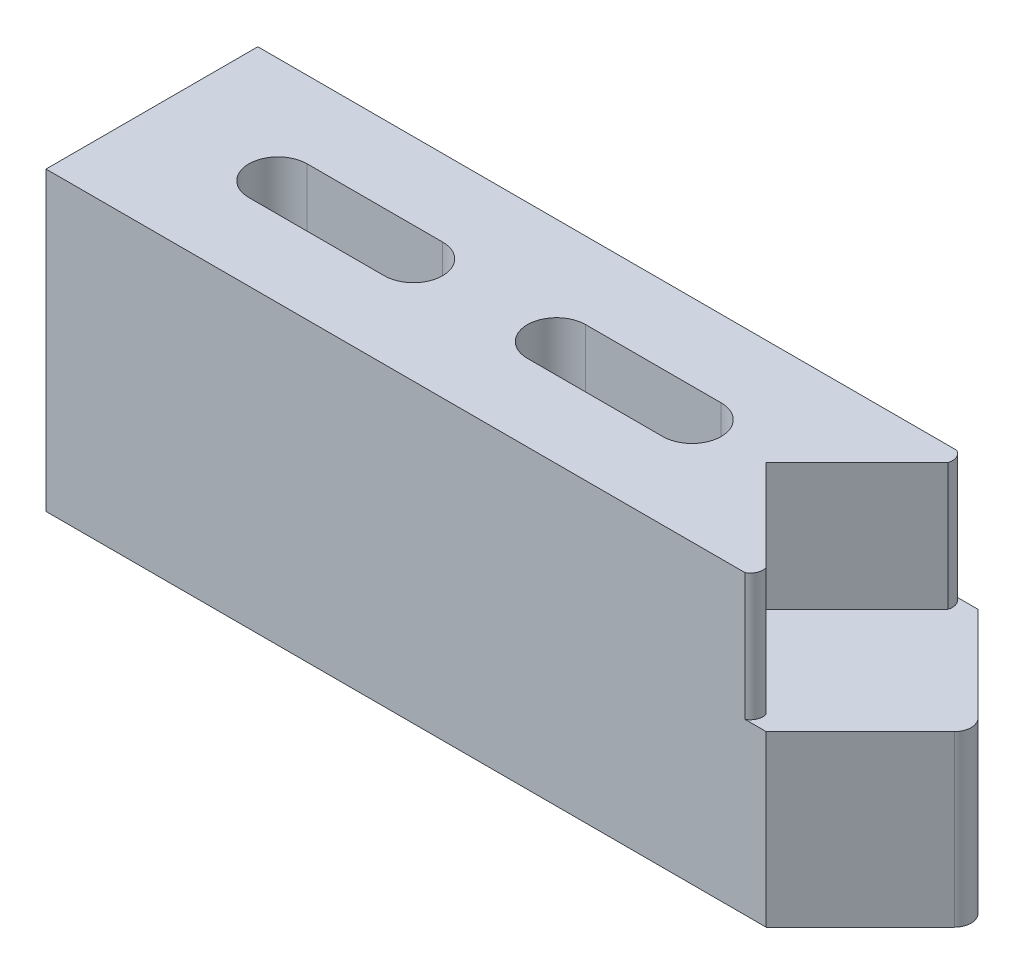
SolidWorks part; units mm, degrees
ref_plane "Front Plane" through (0, 0, 0) normal (0, 0, 1) x (1, 0, 0)
ref_plane "Top Plane" through (0, 0, 0) normal (0, 1, 0) x (1, 0, 0)
ref_plane "Right Plane" through (0, 0, 0) normal (1, 0, 0) x (0, 0, -1)
sketch "Sketch1" plane through (0, 0, 0) normal (0, 0, 1) x (1, 0, 0)
  line L0 (0, 0) -> (43.18, 0)
  line L6 (0, 0) -> (0, 17.78)
  line L10 (0, 17.78) -> (43.18, 17.78)
  line L11 (43.18, 0) -> (43.18, 17.78)
  dimension "D1" = 43.18
  dimension "D2" = 17.78
extrude "Boss-Extrude1" add sketch "Sketch1" against normal blind 12.7
sketch "Sketch3" plane through (0, 17.78, 0) normal (0, 1, 0) x (1, 0, 0)
  line L0 (43.18, 12.7) -> (36.83, 6.35)
  line L1 (36.83, 6.35) -> (43.18, 0)
  line L4 (43.18, 12.7) -> (43.18, 0)
  dimension "D2" = 90
extrude "Cut-Extrude1" cut sketch "Sketch3" against normal blind 7.62
sketch "Sketch4" plane through (0, 17.78, 0) normal (0, 1, 0) x (1, 0, 0)
  line L0 (32.381, 6.35) -> (24.261, 6.35) construction
  line L1 (32.381, 4.6) -> (24.261, 4.6)
  line L2 (32.381, 8.1) -> (24.261, 8.1)
  line L3 (15.681, 6.35) -> (7.561, 6.35) construction
  line L4 (15.681, 4.6) -> (7.561, 4.6)
  line L5 (15.681, 8.1) -> (7.561, 8.1)
  line L6 (43.18, 0) -> (0, 0) construction
  line L7 (0, 12.7) -> (0, 0) construction
  arc A0 (32.381, 4.6) -> (32.381, 8.1) centre (32.381, 6.35) ccw
  arc A1 (24.261, 8.1) -> (24.261, 4.6) centre (24.261, 6.35) ccw
  arc A2 (15.681, 4.6) -> (15.681, 8.1) centre (15.681, 6.35) ccw
  arc A3 (7.561, 8.1) -> (7.561, 4.6) centre (7.561, 6.35) ccw
  point P2 (28.321, 6.35)
  point P7 (11.621, 6.35)
  point P14 (34.131, 6.35)
  point P16 (5.811, 6.35)
  point P18 (17.431, 6.35)
  point P19 (22.511, 6.35)
  dimension "D1" = 1.75
  dimension "D2" = 2.699
  dimension "D3" = 5.811
  dimension "D4" = 6.35
  dimension "D5" = 5.08
extrude "Cut-Extrude2" cut sketch "Sketch4" against normal through all
sketch "Sketch5" plane through (0, 10.16, 0) normal (0, 1, 0) x (1, 0, 0)
  line L0 (43.18, 12.7) -> (49.53, 6.35)
  line L1 (49.53, 6.35) -> (43.18, 0)
  line L2 (43.18, 0) -> (43.18, 12.7) construction
  line L3 (43.18, 0) -> (43.18, 12.7)
  line L4 (36.83, 6.35) -> (43.18, 0) construction
  line L5 (43.18, 12.7) -> (36.83, 6.35) construction
extrude "Boss-Extrude2" add sketch "Sketch5" against normal up to surface (10.16 mm away) up to face at (28.321, 0, -6.35)
sketch "Sketch6" plane through (0, 17.78, 0) normal (0, 1, 0) x (1, 0, 0)
  line L0 (43.18, 12.7) -> (0, 12.7) construction
  line L1 (43.18, 12.7) -> (36.83, 6.35) construction
  line L2 (41.91, 12.7) -> (43.18, 12.7)
  line L3 (43.18, 12.7) -> (42.282, 11.802)
  line L4 (36.83, 6.35) -> (49.2302, 6.35) construction
  line L5 (41.91, 0) -> (43.18, 0)
  line L6 (43.18, 0) -> (42.282, 0.898)
  arc A0 (41.91, 12.7) -> (42.282, 11.802) centre (41.5538, 12.0264) cw
  arc A1 (41.91, 0) -> (42.282, 0.898) centre (41.5538, 0.6736) ccw
  dimension "D3" = 0.762
  dimension "D1" = 1.27
  dimension "D2" = 1.27
extrude "Cut-Extrude3" cut sketch "Sketch6" against normal up to surface (7.62 mm away) up to face at (43.18, 10.16, -6.35)
fillet "Fillet1" radius 1 1 edges at (49.53, 5.08, -6.35)
